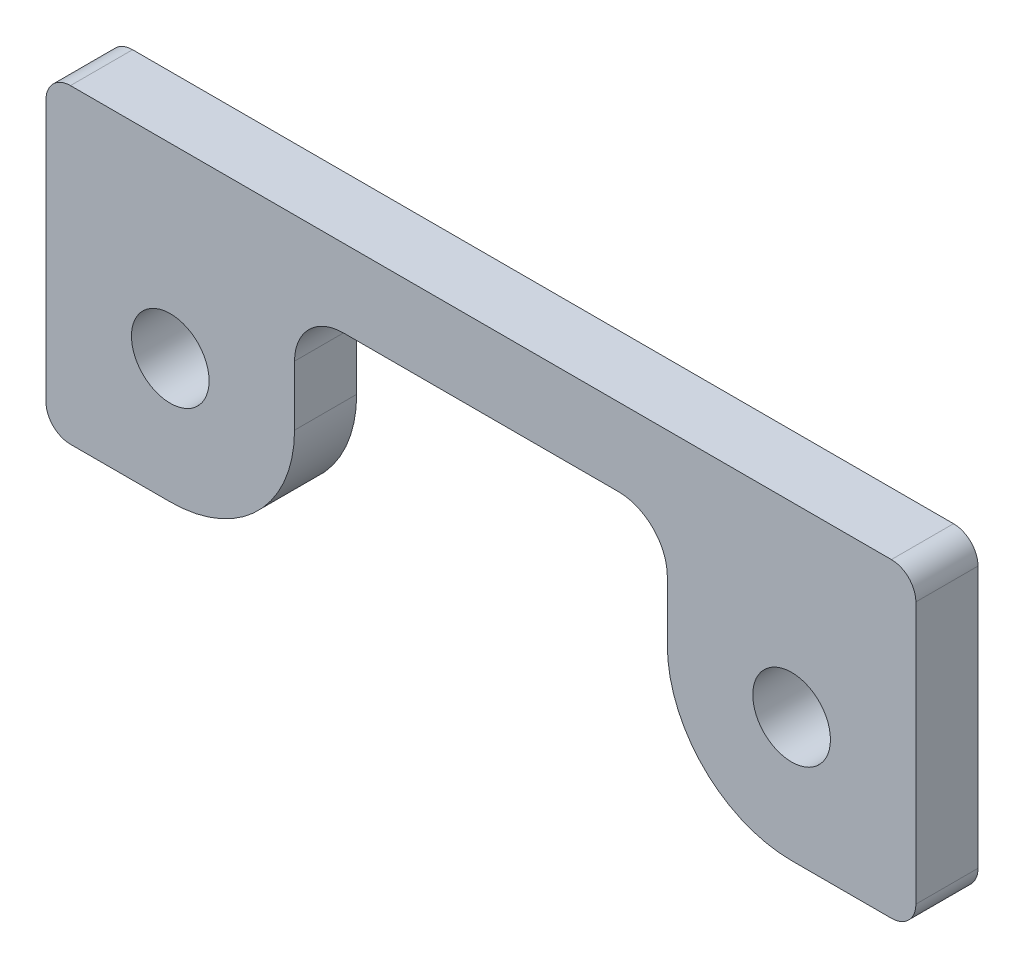
SolidWorks part; units mm, degrees
ref_plane "Front Plane" through (0, 0, 0) normal (0, 0, 1) x (1, 0, 0)
ref_plane "Top Plane" through (0, 0, 0) normal (0, 1, 0) x (1, 0, 0)
ref_plane "Right Plane" through (0, 0, 0) normal (1, 0, 0) x (0, 0, -1)
sketch "Sketch2" plane through (0, 0, 0) normal (0, 0, 1) x (1, 0, 0)
  line L0 (25.4, 38.1) -> (63.5, 38.1) construction
  line L3 (2.5, 38.1) -> (86.4, 38.1)
  line L7 (25.4, 46.04) -> (63.5, 46.04) construction
  line L8 (30.4, 30.16) -> (58.5, 30.16)
  line L9 (12.7, 6.35) -> (2.5, 6.35)
  line L10 (0, 8.85) -> (0, 35.6)
  line L11 (76.2, 6.35) -> (86.4, 6.35)
  line L12 (88.9, 8.85) -> (88.9, 35.6)
  line L13 (25.4, 19.05) -> (25.4, 25.16)
  line L14 (63.5, 19.05) -> (63.5, 25.16)
  line L15 (25.4, 30.16) -> (30.4, 30.16) construction
  line L16 (58.5, 30.16) -> (63.5, 30.16) construction
  circle A0 centre (12.7, 19.05) radius 3.9688
  circle A1 centre (76.2, 19.05) radius 3.9687
  arc A2 (25.4, 46.04) -> (25.4, 30.16) centre (25.4, 38.1) ccw construction
  arc A3 (63.5, 30.16) -> (63.5, 46.04) centre (63.5, 38.1) ccw construction
  arc A4 (12.7, 6.35) -> (25.4, 19.05) centre (12.7, 19.05) ccw
  arc A5 (63.5, 19.05) -> (76.2, 6.35) centre (76.2, 19.05) ccw
  arc A6 (58.5, 30.16) -> (63.5, 25.16) centre (58.5, 25.16) cw
  arc A7 (30.4, 30.16) -> (25.4, 25.16) centre (30.4, 25.16) ccw
  arc A8 (88.9, 8.85) -> (86.4, 6.35) centre (86.4, 8.85) cw
  arc A9 (88.9, 35.6) -> (86.4, 38.1) centre (86.4, 35.6) ccw
  arc A10 (0, 8.85) -> (2.5, 6.35) centre (2.5, 8.85) ccw
  arc A11 (2.5, 38.1) -> (0, 35.6) centre (2.5, 35.6) ccw
  point P0 (0, 0)
  point P4 (44.45, 19.05)
  point P5 (0, 0)
  point P10 (44.45, 38.1)
  point P22 (88.9, 37.3529)
  point P24 (0, 0)
  point P29 (0, 0)
  point P30 (0, 0)
  point P33 (0, 0)
  point P34 (63.5, 38.1)
  point P35 (0, 0)
  point P36 (0, 0)
  point P37 (63.5, 46.04)
  point P38 (0, 0)
  point P39 (44.45, 46.04)
  point P41 (0, 0)
  point P42 (44.45, 19.05)
  dimension "D3" = 7.9375
  dimension "D6" = 7.94
  dimension "D8" = 5
  dimension "D11" = 2.5
  dimension "D1" = 88.9
  dimension "D2" = 38.1
  dimension "D4" = 6.35
  dimension "D5" = 44.45
  dimension "D7" = 38.1
  dimension "D9" = 19.05
  dimension "D10" = 12.7
extrude "Boss-Extrude1" add sketch "Sketch2" along normal blind 6.35
ref_plane "Plane1" through (0, 15.875, -15.875) normal (0, -0.7071, 0.7071) x (1, 0, 0)
sketch "Sketch3" plane through (0, 15.875, -15.875) normal (0, -0.7071, 0.7071) x (1, 0, 0)
  line L0 (86.4, 31.4309) -> (2.5, 31.4309) construction
  line L1 (86.4, 26.9408) -> (2.5, 26.9408) construction
  line L2 (30.4, 21.3263) -> (58.5, 21.3263) construction
  line L3 (30.4, 21.3263) -> (58.5, 21.3263)
  circle A0 centre (49.45, 31.4309) radius 3 construction
  circle A1 centre (39.45, 31.4309) radius 3 construction
  circle A2 centre (32.45, 31.4309) radius 3 construction
  circle A3 centre (56.45, 31.4309) radius 3 construction
  circle A4 centre (44.45, 31.4309) radius 1.5875 construction
  circle A5 centre (27.45, 31.4309) radius 1.5875 construction
  circle A6 centre (61.45, 31.4309) radius 1.5875 construction
  circle A7 centre (44.45, 21.3263) radius 1.59
  circle A8 centre (49.45, 21.3263) radius 3
  circle A9 centre (56.45, 21.3263) radius 3
  circle A10 centre (39.45, 21.3263) radius 3
  circle A11 centre (32.45, 21.3263) radius 3
  circle A12 centre (61.45, 21.3263) radius 1.59
  circle A13 centre (27.45, 21.3263) radius 1.59
  point P12 (44.45, 26.9408)
  point P35 (0, 0)
  point P36 (0, 0)
  dimension "D1" = 6
  dimension "D6" = 3.175
  dimension "D9" = 3.18
  dimension "D10" = 6
  dimension "D2" = 5
  dimension "D3" = 5
  dimension "D4" = 7
  dimension "D5" = 7
  dimension "D7" = 5
  dimension "D8" = 5
  dimension "D11" = 7
  dimension "D12" = 7
  dimension "D13" = 5
  dimension "D14" = 5
  dimension "D15" = 5
  dimension "D16" = 5
extrude "Cut-Extrude1" cut sketch "Sketch3" against normal through all both and the other way through all contours A12 | A9 | L3 A8 | L3 A7 | L3 A10 | A11 | A13 | L3 A8 | L3 A7 | L3 A10 region at (56.45, 33.0163, 1.2663) region at (49.45, 31.8553, 0.1053) region at (49.45, 30.0547, -1.6953) region at (44.45, 31.4322, -0.3178) region at (44.45, 30.4778, -1.2722) region at (39.45, 31.8553, 0.1053) region at (39.45, 30.0547, -1.6953) region at (29.5349, 30.955, -0.795) region at (61.45, 30.955, -0.795) region at (27.45, 30.955, -0.795)
